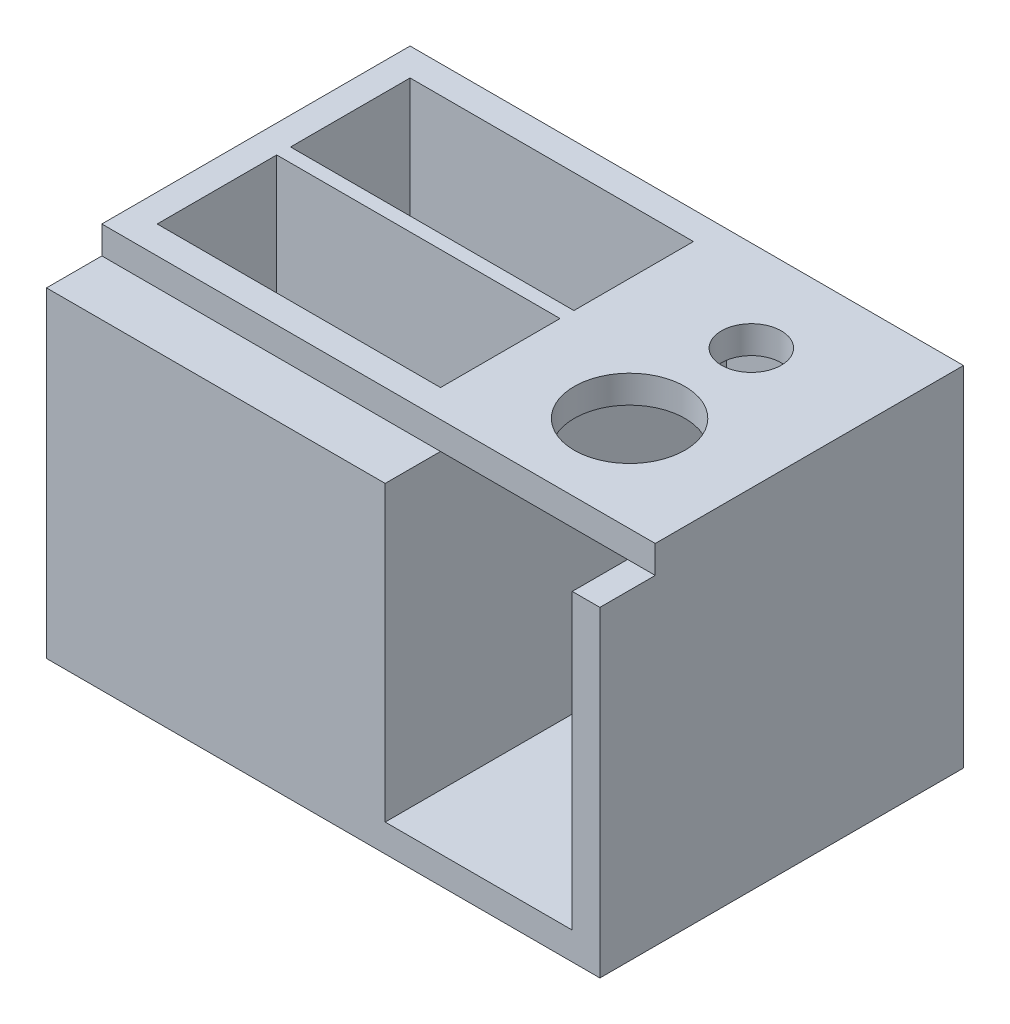
SolidWorks part; units mm, degrees
material "ABS"
ref_plane "Front Plane" through (0, 0, 0) normal (0, 0, 1) x (1, 0, 0)
ref_plane "Top Plane" through (0, 0, 0) normal (0, 1, 0) x (1, 0, 0)
ref_plane "Right Plane" through (0, 0, 0) normal (1, 0, 0) x (0, 0, -1)
sketch "Sketch1" plane through (0, 0, 0) normal (0, 1, 0) x (1, 0, 0)
  line L0 (3.175, 18.4785) -> (3.175, 32.1945)
  line L1 (0, 0) -> (63.5, 0)
  line L2 (0, 0) -> (0, 44.45)
  line L3 (0, 44.45) -> (63.5, 44.45)
  line L4 (63.5, 0) -> (63.5, 44.45)
  line L5 (4.445, 4.445) -> (34.417, 4.445)
  line L6 (4.445, 4.445) -> (4.445, 15.621)
  line L7 (4.445, 15.621) -> (34.417, 15.621)
  line L8 (34.417, 4.445) -> (34.417, 15.621)
  line L9 (4.445, 19.7485) -> (34.417, 19.7485)
  line L10 (4.445, 19.7485) -> (4.445, 30.9245)
  line L11 (4.445, 30.9245) -> (34.417, 30.9245)
  line L12 (34.417, 19.7485) -> (34.417, 30.9245)
  line L13 (3.175, 32.1945) -> (35.687, 32.1945)
  line L14 (35.687, 18.4785) -> (35.687, 32.1945)
  line L15 (3.175, 18.4785) -> (35.687, 18.4785)
  line L16 (3.175, 3.175) -> (35.687, 3.175)
  line L17 (35.687, 3.175) -> (35.687, 16.891)
  line L18 (3.175, 16.891) -> (35.687, 16.891)
  line L19 (3.175, 3.175) -> (3.175, 16.891)
  dimension "D1" = 44.45
  dimension "D2" = 63.5
  dimension "D3" = 11.176
  dimension "D4" = 29.972
  dimension "D5" = 11.176
  dimension "D6" = 29.972
  dimension "D9" = 1.5875
  dimension "D10" = 3.175
  dimension "D11" = 3.175
  dimension "D7" = 1.27
  dimension "D8" = 1.27
extrude "Boss-Extrude1" add sketch "Sketch1" along normal blind 40.005 contours L16 L19 L18 L17 L1 L4 L3 L2 L15 L0 L13 L14 region at (37.4406, 0, -24.3223)
sketch "Sketch2" plane through (0, 0, 0) normal (0, -1, 0) x (1, 0, 0)
  line L0 (3.175, -32.1945) -> (35.687, -32.1945) construction
  line L1 (3.175, -18.4785) -> (3.175, -32.1945) construction
  line L2 (3.175, -18.4785) -> (35.687, -18.4785) construction
  line L3 (35.687, -18.4785) -> (35.687, -32.1945) construction
  line L4 (0, 0) -> (0, -44.45)
  line L5 (0, -44.45) -> (63.5, -44.45)
  line L6 (63.5, -44.45) -> (63.5, 0)
  line L7 (63.5, 0) -> (0, 0)
  line L8 (0, 0) -> (0, -44.45)
  line L9 (0, -44.45) -> (63.5, -44.45)
  line L10 (63.5, -44.45) -> (63.5, 0)
  line L11 (63.5, 0) -> (0, 0)
  line L12 (35.687, -3.175) -> (35.687, -16.891) construction
  line L13 (3.175, -3.175) -> (35.687, -3.175) construction
  line L14 (3.175, -3.175) -> (3.175, -16.891) construction
  line L15 (3.175, -16.891) -> (35.687, -16.891) construction
  line L16 (3.175, -32.1945) -> (35.687, -32.1945)
  line L17 (3.175, -18.4785) -> (3.175, -32.1945)
  line L18 (3.175, -18.4785) -> (35.687, -18.4785)
  line L19 (35.687, -18.4785) -> (35.687, -32.1945)
  line L20 (35.687, -3.175) -> (35.687, -16.891)
  line L21 (3.175, -3.175) -> (35.687, -3.175)
  line L22 (3.175, -3.175) -> (3.175, -16.891)
  line L23 (3.175, -16.891) -> (35.687, -16.891)
  line M9 (3.175, -18.4785) -> (35.687, -18.4785)
  line M10 (35.687, -18.4785) -> (35.687, -32.1945)
  line M11 (35.687, -32.1945) -> (3.175, -32.1945)
  line M12 (3.175, -32.1945) -> (3.175, -18.4785)
  line M13 (3.175, -3.175) -> (35.687, -3.175)
  line M14 (35.687, -3.175) -> (35.687, -16.891)
  line M15 (35.687, -16.891) -> (3.175, -16.891)
  line M16 (3.175, -16.891) -> (3.175, -3.175)
  dimension "D1" = 0
extrude "Boss-Extrude2" add sketch "Sketch2" against normal blind 2.54 contours M13 M16 M15 M14 | M9 M12 M11 M10 region at (19.431, 0, -25.3365) region at (19.431, 0, -10.033)
sketch "Sketch3" plane through (0, 40.005, 0) normal (0, 1, 0) x (1, 0, 0)
  line L33 (35.687, 35.3695) -> (3.175, 35.3695)
  line L34 (35.687, 35.3695) -> (3.175, 35.3695)
  line L36 (0, 32.1945) -> (0, 18.4785)
  line L37 (0, 32.1945) -> (0, 18.4785)
  line L38 (0, 0) -> (63.5, 0) construction
  line L39 (38.862, 18.4785) -> (38.862, 32.1945)
  line L40 (38.862, 18.4785) -> (38.862, 32.1945)
  line L41 (0, 35.3695) -> (38.862, 35.3695)
  line L42 (0, 35.3695) -> (0, 0)
  line L43 (0, 0) -> (38.862, 0)
  line L44 (38.862, 35.3695) -> (38.862, 0)
  line L49 (0, 44.45) -> (0, 0)
  line L50 (0, 0) -> (63.5, 0)
  line L51 (63.5, 0) -> (63.5, 44.45)
  line L52 (63.5, 44.45) -> (0, 44.45)
  line L53 (0, 44.45) -> (0, 0)
  line L54 (0, 0) -> (63.5, 0)
  line L55 (63.5, 0) -> (63.5, 44.45)
  line L56 (63.5, 44.45) -> (0, 44.45)
  line M11 (0, 44.45) -> (0, 0)
  line M12 (0, 0) -> (63.5, 0)
  line M13 (63.5, 0) -> (63.5, 44.45)
  line M14 (63.5, 44.45) -> (0, 44.45)
  dimension "D4" = 0
  dimension "D1" = 3.175
  dimension "D2" = 3.175
  dimension "D3" = 3.175
extrude "Cut-Extrude1" cut sketch "Sketch3" against normal blind 36.83 contours L41 L44 L40 L42 L37 L34 M12 M13 M14 M11 region at (43.4436, 40.005, -26.5347)
sketch "Sketch9" plane through (0, 0, 0) normal (0, 0, 1) x (1, 0, 0)
  line L0 (38.862, 3.175) -> (38.862, 40.005) construction
  line L1 (0, 40.005) -> (38.862, 40.005)
  line L2 (0, 40.005) -> (0, 36.83)
  line L3 (0, 36.83) -> (38.862, 36.83)
  line L4 (38.862, 40.005) -> (38.862, 36.83)
  line L11 (63.5, 3.175) -> (38.862, 3.175)
  line L12 (38.862, 3.175) -> (38.862, 40.005)
  line L13 (38.862, 40.005) -> (0, 40.005)
  line L14 (0, 40.005) -> (0, 0)
  line L15 (0, 0) -> (63.5, 0)
  line L16 (63.5, 0) -> (63.5, 3.175)
  line L18 (38.862, 3.175) -> (38.862, 40.005)
  line L19 (38.862, 40.005) -> (0, 40.005)
  line L20 (0, 40.005) -> (0, 0)
  line L21 (0, 0) -> (63.5, 0)
  line L22 (63.5, 0) -> (63.5, 3.175)
  line L23 (63.5, 3.175) -> (38.862, 3.175)
  line M12 (38.862, 3.175) -> (38.862, 40.005)
  line M14 (0, 40.005) -> (0, 0)
  line M15 (0, 0) -> (63.5, 0)
  line M16 (63.5, 0) -> (63.5, 3.175)
  dimension "D1" = 3.175
  dimension "D2" = 0
extrude "Boss-Extrude8" add sketch "Sketch9" along normal blind 6.35 contours L3 M14 M15 M16 M12 region at (21.0763, 17.543, 0)
sketch "Sketch10" plane through (0, 0, 6.35) normal (0, 0, 1) x (1, 0, 0)
  line L0 (0, 36.83) -> (38.862, 36.83) construction
  line L1 (63.5, 3.175) -> (60.325, 3.175)
  line L2 (63.5, 3.175) -> (63.5, 36.83)
  line L3 (63.5, 36.83) -> (60.325, 36.83)
  line L4 (60.325, 3.175) -> (60.325, 36.83)
  line L5 (38.862, 3.175) -> (38.862, 36.83) construction
  line L7 (60.325, 36.83) -> (60.325, 33.655)
  line L11 (60.325, 33.655) -> (60.325, 30.48)
  line L14 (60.325, 36.83) -> (38.862, 36.83)
  line L15 (60.325, 36.83) -> (60.325, 33.655)
  line L16 (60.325, 33.655) -> (38.862, 33.655)
  line L17 (38.862, 36.83) -> (38.862, 33.655)
  line M8 (63.5, 3.175) -> (38.862, 3.175)
  line M9 (38.862, 3.175) -> (38.862, 36.83)
  dimension "D1" = 3.175
  dimension "D2" = 3.175
  dimension "D3" = 3.175
extrude "Boss-Extrude9" add sketch "Sketch10" against normal up to surface (50.8 mm away) contours L4 L2 L3 M8 | L16 L4 L14 M9 region at (61.9125, 20.0025, 6.35) region at (49.5935, 35.2425, 6.35) up to face at (31.75, 1.5875, -44.45)
sketch "Sketch11" plane through (0, 0, 0) normal (-1, 0, 0) x (0, 0, 1)
  line L1 (-35.3695, 36.83) -> (-44.45, 36.83)
  line L2 (-35.3695, 36.83) -> (-35.3695, 0)
  line L3 (-35.3695, 0) -> (-44.45, 0)
  line L4 (-44.45, 36.83) -> (-44.45, 0)
extrude "Cut-Extrude2" cut sketch "Sketch11" against normal through all
sketch "Sketch12" plane through (0, 0, -35.3695) normal (0, 0, -1) x (-1, 0, 0)
  line L0 (-49.5935, 18.415) -> (-49.5935, 8.997) construction
  line L1 (-60.325, 33.655) -> (-38.862, 33.655)
  line L2 (-60.325, 33.655) -> (-60.325, 3.175)
  line L3 (-60.325, 3.175) -> (-38.862, 3.175)
  line L4 (-38.862, 33.655) -> (-38.862, 3.175)
  line L5 (-44.5135, 18.415) -> (-44.5135, 8.997)
  line L6 (-54.6735, 18.415) -> (-54.6735, 8.997)
  line L7 (-60.325, 33.655) -> (-38.862, 3.175) construction
  circle A0 centre (-49.5935, 18.415) radius 5.08
  arc A1 (-44.5135, 18.415) -> (-54.6735, 18.415) centre (-49.5935, 18.415) ccw
  arc A2 (-54.6735, 8.997) -> (-44.5135, 8.997) centre (-49.5935, 8.997) ccw
  point P8 (-49.5935, 13.706)
  point P14 (-49.5935, 18.415)
  point P15 (-49.5935, 8.997)
  line M1 (-38.862, 33.655) -> (-38.862, 3.175)
  line M2 (-38.862, 3.175) -> (-60.325, 3.175)
  line M3 (-60.325, 3.175) -> (-60.325, 33.655)
  line M4 (-60.325, 33.655) -> (-38.862, 33.655)
  dimension "D1" = 10.16
extrude "Boss-Extrude10" add sketch "Sketch12" against normal blind 2.54 contours A0 M1 M4 M3 M2 region at (49.5935, 33.2822, -35.3695)
sketch "Sketch13" plane through (0, 36.83, 0) normal (0, 1, 0) x (1, 0, 0)
  line L0 (63.5, 35.3695) -> (63.5, -6.35) construction
  line L1 (38.862, 35.3695) -> (63.5, 35.3695)
  line L2 (38.862, 35.3695) -> (38.862, 0)
  line L3 (38.862, 0) -> (63.5, 0)
  line L4 (63.5, 35.3695) -> (63.5, 0)
extrude "Boss-Extrude11" add sketch "Sketch13" along normal blind 3.175
sketch "Sketch14" plane through (0, 40.005, 0) normal (0, 1, 0) x (1, 0, 0)
  line L0 (0, 0) -> (63.5, 0) construction
  line L1 (35.687, 0) -> (63.5, 0)
  line L2 (35.687, 0) -> (35.687, 35.3695)
  line L3 (35.687, 35.3695) -> (63.5, 35.3695)
  line L4 (63.5, 0) -> (63.5, 35.3695)
  line L5 (63.5, 0) -> (63.5, 35.3695) construction
  line L6 (0, 35.3695) -> (63.5, 35.3695) construction
  line L7 (49.5935, 35.3695) -> (49.5935, 0) construction
  circle A0 centre (49.5935, 10.9621) radius 6.35
  point P12 (49.5935, 10.9621)
  dimension "D1" = 12.7
extrude "Cut-Extrude3" cut sketch "Sketch14" against normal blind 7.62 contours A0 | L7 A0 region at (46.8985, 40.005, -10.9621) region at (52.2885, 40.005, -10.9621)
sketch "Sketch15" plane through (0, 40.005, 0) normal (0, 1, 0) x (1, 0, 0)
  line L0 (49.5935, 10.9621) -> (49.5935, 24.9321)
  line L1 (63.5, 0) -> (63.5, 35.3695) construction
  circle A0 centre (49.5935, 24.9321) radius 3.429
  dimension "D1" = 6.858
  dimension "D2" = 0
  dimension "D3" = 13.97
extrude "Cut-Extrude4" cut sketch "Sketch15" against normal blind 10.16 contours A0 region at (51.9496, 40.005, -22.576)
sketch "Sketch17" plane through (0, 0, 6.35) normal (0, 0, 1) x (1, 0, 0)
  line L0 (0, 36.83) -> (63.5, 36.83) construction
  line L1 (38.862, 33.655) -> (60.325, 33.655)
  line L2 (38.862, 33.655) -> (38.862, 36.83)
  line L3 (38.862, 36.83) -> (60.325, 36.83)
  line L4 (60.325, 33.655) -> (60.325, 36.83)
extrude "Cut-Extrude5" cut sketch "Sketch17" along direction (0, 0, -1) on the side against the normal up to surface (39.1795 mm away) up to face at (49.5935, 13.706, -32.8295)
